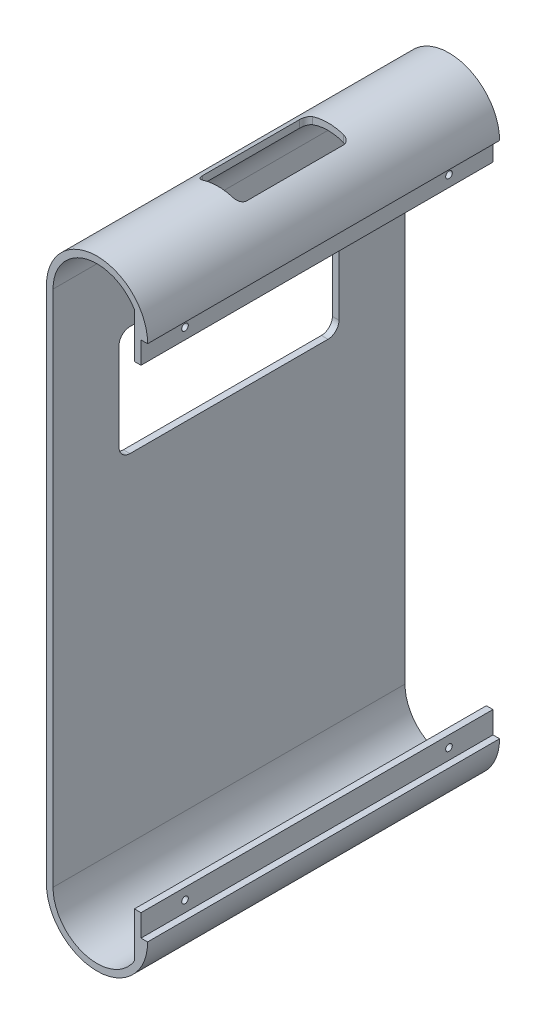
SolidWorks part; units mm, degrees
ref_plane "Front Plane" through (0, 0, 0) normal (0, 0, 1) x (1, 0, 0)
ref_plane "Top Plane" through (0, 0, 0) normal (0, 1, 0) x (1, 0, 0)
ref_plane "Right Plane" through (0, 0, 0) normal (1, 0, 0) x (0, 0, -1)
sketch "Sketch1" plane through (0, 0, 0) normal (0, 0, 1) x (1, 0, 0)
  line L0 (0, -75) -> (-40, -75) construction
  line L1 (33, 42.75) -> (-40, 42.75) construction
  line L3 (-40, -75) -> (-40, 160.5)
  line L4 (-43, -75) -> (-43, 160.5)
  line L5 (0, 160.5) -> (3, 160.5)
  line L6 (0, -75) -> (3, -75)
  arc A0 (-40, -75) -> (0, -75) centre (-20, -75) ccw
  arc A1 (-40, 160.5) -> (0, 160.5) centre (-20, 160.5) cw
  arc A2 (-43, 160.5) -> (3, 160.5) centre (-20, 160.5) cw
  arc A3 (-43, -75) -> (3, -75) centre (-20, -75) ccw
  dimension "D1" = 3
extrude "Boss-Extrude1" add sketch "Sketch1" against normal up to surface (160 mm away)
ref_plane "Plane1" through (3, 0, 0) normal (1, 0, 0) x (0, 0, -1)
sketch "Sketch5" plane through (0, 0, -160) normal (0, 0, -1) x (-1, 0, 0)
  line L0 (43, 42.75) -> (-4.5, 42.75) construction
  line L1 (3, -65) -> (0, -65)
  line L2 (3, -65) -> (3, -86.3578)
  line L3 (3, -86.3578) -> (0, -86.3578)
  line L4 (0, -65) -> (0, -86.3578)
  line L5 (43, 160.5) -> (43, -75) construction
  line L6 (0, 150.5) -> (0, 171.8578)
  line L7 (3, 171.8578) -> (0, 171.8578)
  line L8 (3, 150.5) -> (3, 171.8578)
  line L9 (3, 150.5) -> (0, 150.5)
  arc A0 (-3, -75) -> (43, -75) centre (20, -75) ccw construction
extrude "Boss-Extrude4" add sketch "Sketch5" against normal up to surface (160 mm away) up to face at (-20, 42.75, 0)
sketch "Sketch7" plane through (-3, 0, 0) normal (-1, 0, 0) x (0, 0, 1)
  line L0 (0, -65) -> (-160, -65) construction
  line L1 (0, -65) -> (-160, -65) construction
  line L2 (0, 150.5) -> (-160, 150.5) construction
  line L3 (0, 150.5) -> (-160, 150.5) construction
  line L4 (-160, 160.5) -> (-160, -75) construction
  line L5 (0, 160.5) -> (0, -75) construction
  line L6 (-160, 42.75) -> (0, 42.75) construction
  circle A0 centre (-140, -70) radius 1.5
  circle A1 centre (-20, -70) radius 1.5
  circle A2 centre (-20, 155.5) radius 1.5
  circle A3 centre (-140, 155.5) radius 1.5
  dimension "D1" = 5
  dimension "D2" = 20
  dimension "D4" = 5
  dimension "D3" = 20
extrude "Cut-Extrude2" cut sketch "Sketch7" against normal through all
sketch "Sketch8" plane through (-43, 0, 0) normal (-1, 0, 0) x (0, 0, 1)
  line L0 (-30, 123.2573) -> (-30, 83.2573) construction
  line L1 (-125, 128.2573) -> (-35, 128.2573)
  line L2 (-130, 123.2573) -> (-130, 83.2573)
  line L3 (-125, 78.2573) -> (-35, 78.2573)
  line L4 (-30, 123.2573) -> (-30, 83.2573)
  line L5 (-35, 78.2573) -> (-125, 78.2573) construction
  line L6 (-130, 83.2573) -> (-130, 123.2573) construction
  line L7 (-125, 128.2573) -> (-35, 128.2573) construction
  arc A0 (-125, 128.2573) -> (-130, 123.2573) centre (-125, 123.2573) ccw
  arc A1 (-130, 83.2573) -> (-125, 78.2573) centre (-125, 83.2573) ccw
  arc A2 (-35, 78.2573) -> (-30, 83.2573) centre (-35, 83.2573) ccw
  arc A3 (-35, 128.2573) -> (-30, 123.2573) centre (-35, 123.2573) cw
  dimension "D5" = 5
  dimension "D1" = 0
  dimension "D2" = 0
  dimension "D3" = 0
  dimension "D4" = 0
extrude "Cut-Extrude3" cut sketch "Sketch8" against normal up to surface (3 mm away) up to face at (-40, 42.75, -80)
sketch "Sketch9" plane through (0, 128.2573, 0) normal (0, -1, 0) x (1, 0, 0)
  line L0 (-43, -80) -> (3, -80) construction
  line L1 (-43, -160) -> (-43, 0) construction
  line L2 (3, -160) -> (3, 0) construction
  line L3 (-20, -80) -> (-20, 0) construction
  line L4 (-27, -105) -> (-13, -105)
  line L5 (-30, -102) -> (-30, -58)
  line L6 (-27, -55) -> (-13, -55)
  line L7 (-10, -102) -> (-10, -58)
  line L8 (-20, -160) -> (-20, 0) construction
  arc A0 (-30, -58) -> (-27, -55) centre (-27, -58) cw
  arc A1 (-13, -55) -> (-10, -58) centre (-13, -58) cw
  arc A2 (-13, -105) -> (-10, -102) centre (-13, -102) ccw
  arc A3 (-27, -105) -> (-30, -102) centre (-27, -102) cw
  point P16 (-30, -55)
  point P19 (-10, -55)
  point P22 (-10, -105)
  dimension "D5" = 3
  dimension "D1" = 20
  dimension "D2" = 10
  dimension "D3" = 50
  dimension "D4" = 25
extrude "Cut-Extrude4" cut sketch "Sketch9" against normal through all both and the other way through all
